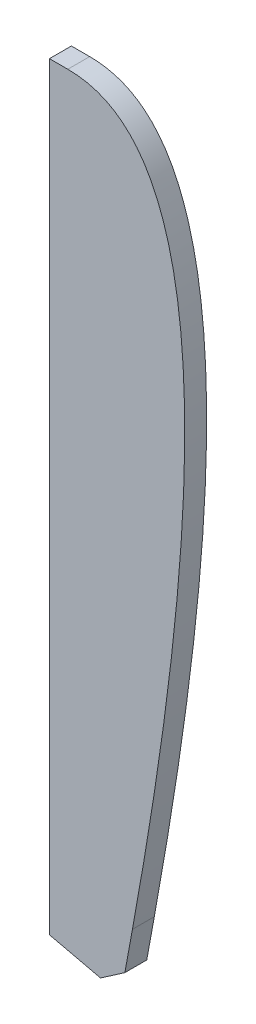
SolidWorks part; units mm, degrees
material "MDF"
ref_plane "Front Plane" through (0, 0, 0) normal (0, 0, 1) x (1, 0, 0)
ref_plane "Top Plane" through (0, 0, 0) normal (0, 1, 0) x (1, 0, 0)
ref_plane "Right Plane" through (0, 0, 0) normal (1, 0, 0) x (0, 0, -1)
sketch "Sketch2" plane through (0, 0, 0) normal (0, 0, 1) x (1, 0, 0)
  line L0 (12.7, -5480.4165) -> (54.1406, -5490.0476)
  line L1 (12.7, -5040.3314) -> (12.7, -5577.1295) construction
  line L2 (48.0775, -5488.6385) -> (326.4096, -5553.3247) construction
  line L3 (12.7, -5480.4165) -> (12.7, -5040.3314)
  line L4 (54.1406, -5490.0476) -> (136.525, -5040.3314)
  line L5 (136.525, -5040.3314) -> (12.7, -5040.3314)
  dimension "D1" = 457.2
  dimension "D2" = 42.545
  dimension "D3" = 123.825
extrude "Boss-Extrude1" add sketch "Sketch2" against normal blind 12.7
fillet "Fillet1" radius 406.4 1 edges at (136.525, -5040.3314, -6.35)
chamfer "Chamfer1" distance 12.7 angle 45 1 edges at (54.1406, -5490.0476, -6.35)
hole_wizard "Hole1" positions "Sketch3" profile "Sketch4" legacy
sketch "Sketch3" plane through (-19.05, -5578.3233, -94.7395) normal (-1, 0, 0) x (0, 0, 1)
  line L0 (218.5638, 29.4548) -> (218.5638, 115.5175) construction
  line L4 (202.6895, 537.9919) -> (202.6895, 97.9067) construction
  line L9 (88.3895, 537.9919) -> (88.3895, 97.9067) construction
  line L13 (104.2638, 29.4548) -> (104.2638, 235.8996) construction
  line L16 (0, 537.9919) -> (0, 29.4548) construction
  point P0 (218.5638, 102.8175)
  point P2 (218.5638, 48.5048)
  point P33 (202.6895, 123.3067)
  point P35 (202.6895, 317.9493)
  point P37 (202.6895, 518.9419)
  point P51 (88.3895, 518.9419)
  point P53 (88.3895, 317.9493)
  point P55 (88.3895, 123.3067)
  point P69 (104.2638, 216.8496)
  point P71 (104.2638, 132.6772)
  point P73 (104.2638, 48.5048)
  point P83 (-104.2638, 48.5048)
  point P84 (-104.2638, 132.6772)
  point P85 (-104.2638, 216.8496)
  point P86 (-88.3895, 123.3067)
  point P87 (-88.3895, 317.9493)
  point P88 (-88.3895, 518.9419)
  point P89 (-202.6895, 518.9419)
  point P90 (-202.6895, 317.9493)
  point P91 (-202.6895, 123.3067)
  point P92 (-218.5638, 48.5048)
  point P93 (-218.5638, 102.8175)
sketch "Sketch4" plane through (-19.05, -5475.5058, 123.8243) normal (0, 1, 0) x (0, 0, 1)
  line L0 (0, 0) -> (0, 51.7539)
  line L1 (0, 51.7539) -> (1.5875, 50.8)
  line L2 (1.5875, 50.8) -> (1.5875, 4.0177)
  line L3 (1.5875, 4.0177) -> (5.08, 0)
  line L4 (5.08, 0) -> (0, 0)
  line L5 (0, -14.3089) -> (0, 102.4216) construction
  line L6 (0, 51.7539) -> (-1.5875, 50.8) construction
  line L7 (-1.5875, 4.0177) -> (-5.08, 0) construction
  dimension "Diameter" = 3.175
  dimension "Depth" = 50.8
  dimension "C-Sink Diameter" = 10.16
  dimension "C-Sink Angle" = 82
  dimension "Drill Angle" = 118
